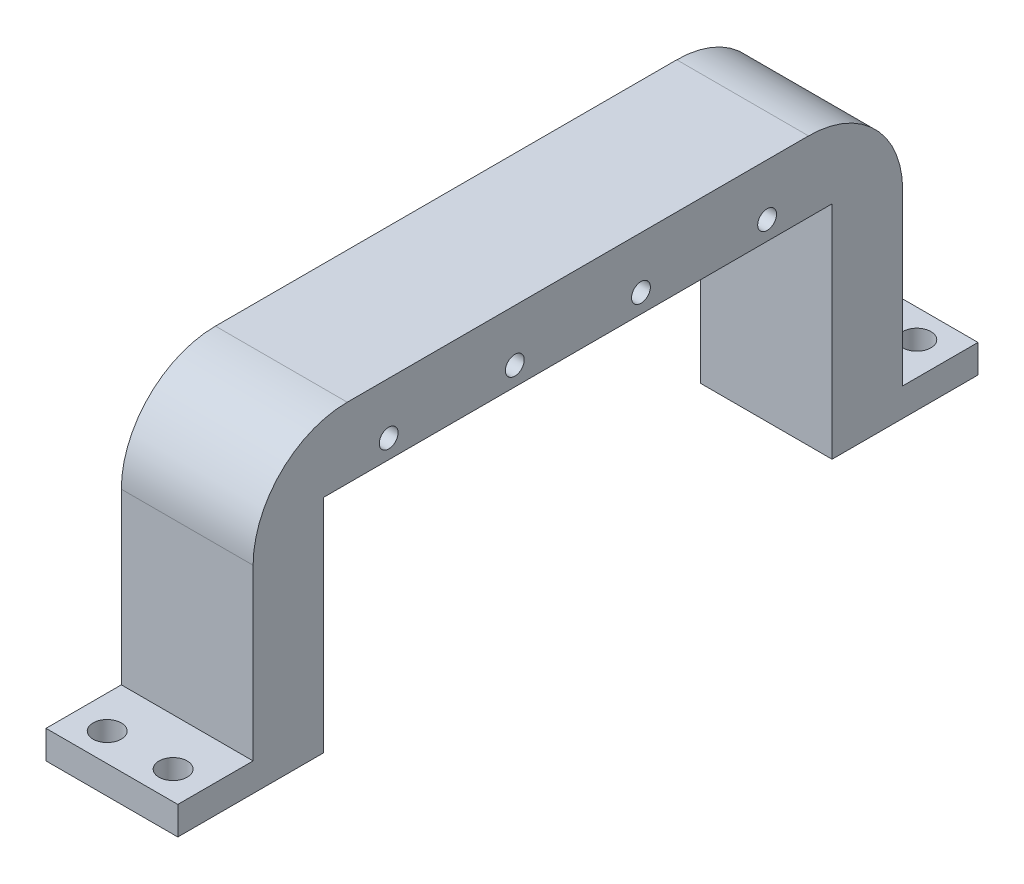
SolidWorks part; units mm, degrees
ref_plane "Front Plane" through (0, 0, 0) normal (0, 0, 1) x (1, 0, 0)
ref_plane "Top Plane" through (0, 0, 0) normal (0, 1, 0) x (1, 0, 0)
ref_plane "Right Plane" through (0, 0, 0) normal (1, 0, 0) x (0, 0, -1)
sketch "Sketch1" plane through (0, 0, 0) normal (1, 0, 0) x (0, 0, -1)
  line L0 (0, 0) -> (0, 9.568) construction
  line L1 (-27, 0) -> (27, 0)
  line L2 (27, 0) -> (27, -23.5)
  line L3 (27, -23.5) -> (34.5, -23.5)
  line L4 (34.5, -23.5) -> (34.5, 7.5)
  line L5 (34.5, 7.5) -> (-34.5, 7.5)
  line L6 (-34.5, -23.5) -> (-34.5, 7.5)
  line L7 (-27, -23.5) -> (-34.5, -23.5)
  line L8 (-27, 0) -> (-27, -23.5)
  point P9 (0, 7.5)
  dimension "D1" = 54
  dimension "D2" = 7.5
  dimension "D3" = 7.5
  dimension "D4" = 23.5
extrude "Boss-Extrude1" add sketch "Sketch1" along normal blind 7 and the other way blind 7
fillet "Fillet1" radius 10 2 edges at (0, 7.5, 34.5) (0, 7.5, -34.5)
sketch "Sketch2" plane through (7, 0, 0) normal (1, 0, 0) x (0, 0, -1)
  line L0 (0, 0) -> (0, 7.5) construction
  line L1 (24.5, 7.5) -> (-24.5, 7.5) construction
  line L2 (-27, 0) -> (27, 0) construction
  circle A0 centre (-6.7, 2) radius 1
  circle A1 centre (-20.1, 2) radius 1
  circle A2 centre (20.1, 2) radius 1
  circle A3 centre (6.7, 2) radius 1
  dimension "D4" = 2
  dimension "D5" = 2
  dimension "D1" = 2
  dimension "D2" = 6.7
  dimension "D3" = 13.4
extrude "Cut-Extrude1" cut sketch "Sketch2" against normal through all
sketch "Sketch3" plane through (0, -23.5, 0) normal (0, -1, 0) x (1, 0, 0)
  line L0 (0, -27) -> (0, -34.5) construction
  line L1 (-7, -27) -> (7, -27) construction
  line L2 (-7, -34.5) -> (7, -34.5) construction
  line L3 (-7, -30.75) -> (7, -30.75) construction
  line L4 (-7, -27) -> (-7, -34.5) construction
  line L5 (7, -27) -> (7, -34.5) construction
  line L6 (0, 0) -> (7, 0) construction
  line L7 (7, 27) -> (7, -27) construction
  circle A0 centre (-3.5, -30.75) radius 1.5
  circle A1 centre (3.5, -30.75) radius 1.5
  circle A2 centre (-3.5, 30.75) radius 1.5
  circle A3 centre (3.5, 30.75) radius 1.5
  dimension "D1" = 3
  dimension "D2" = 3.5
extrude "Cut-Extrude2" cut sketch "Sketch3" against normal blind 5
sketch "Sketch4" plane through (0, -23.5, 0) normal (0, -1, 0) x (1, 0, 0)
  line L0 (0, 0) -> (7, 0) construction
  line L1 (-7, 34.5) -> (7, 34.5)
  line L2 (-7, 34.5) -> (-7, 42.5)
  line L3 (-7, 42.5) -> (7, 42.5)
  line L4 (7, 34.5) -> (7, 42.5)
  line L5 (7, 27) -> (7, -27) construction
  line L6 (7, 34.5) -> (7, 27) construction
  line L7 (0, 39.5) -> (0, 42.5) construction
  line L8 (0, -39.5) -> (0, -42.5) construction
  line L9 (-7, -39.5) -> (7, -39.5) construction
  line L10 (7, -34.5) -> (7, -42.5)
  line L11 (-7, -42.5) -> (7, -42.5)
  line L12 (-7, -34.5) -> (-7, -42.5)
  line L13 (-7, -34.5) -> (7, -34.5)
  circle A0 centre (-3.5, 39.5) radius 1.5
  circle A1 centre (3.5, 39.5) radius 1.5
  circle A2 centre (3.5, -39.5) radius 1.5
  circle A3 centre (-3.5, -39.5) radius 1.5
  point P10 (0, 0)
  dimension "D4" = 3
  dimension "D1" = 8
  dimension "D2" = 3.5
  dimension "D3" = 3
extrude "Boss-Extrude2" add sketch "Sketch4" against normal blind 3
